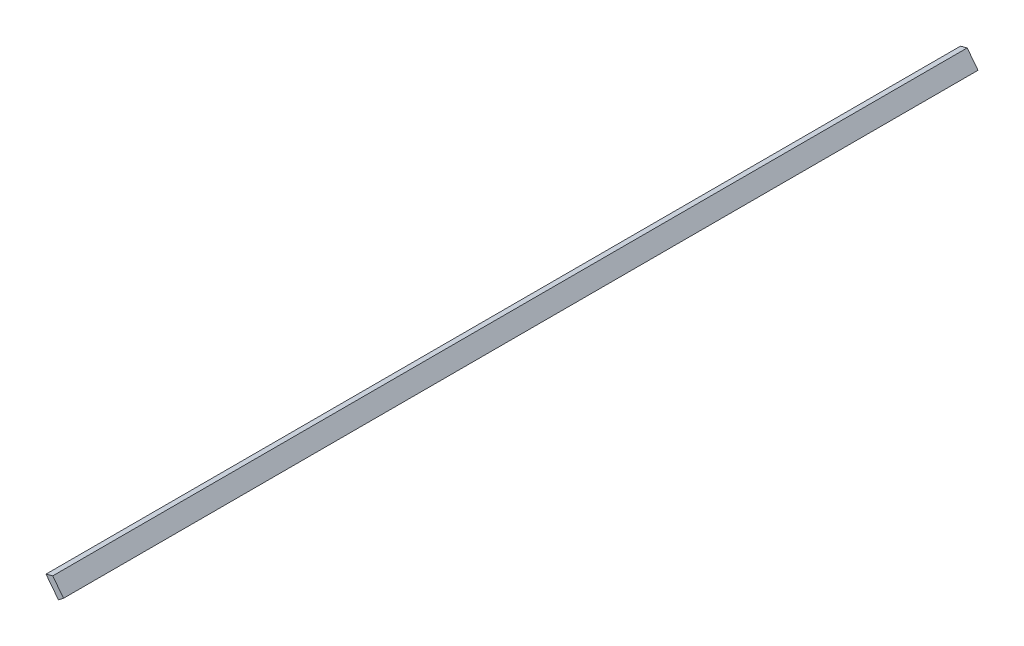
SolidWorks part; units mm, degrees
ref_plane "Front Plane" through (0, 0, 0) normal (0, 0, 1) x (1, 0, 0)
ref_plane "Top Plane" through (0, 0, 0) normal (0, 1, 0) x (1, 0, 0)
ref_plane "Right Plane" through (0, 0, 0) normal (1, 0, 0) x (0, 0, -1)
sketch "Sketch1" plane through (0, 0, 0) normal (0, 0, 1) x (1, 0, 0)
  line L0 (0, 0) -> (5.0245, 3.8829)
  line L1 (5.0245, 3.8829) -> (-5.637, 17.6791)
  line L2 (-5.637, 17.6791) -> (-12.2698, 15.8775)
  line L3 (-12.2698, 15.8775) -> (0, 0)
  dimension "D1" = 6.35
  dimension "D2" = 67.5
  dimension "D3" = 90
  dimension "D4" = 20.066
extrude "Boss-Extrude1" add sketch "Sketch1" along normal blind 901.7
